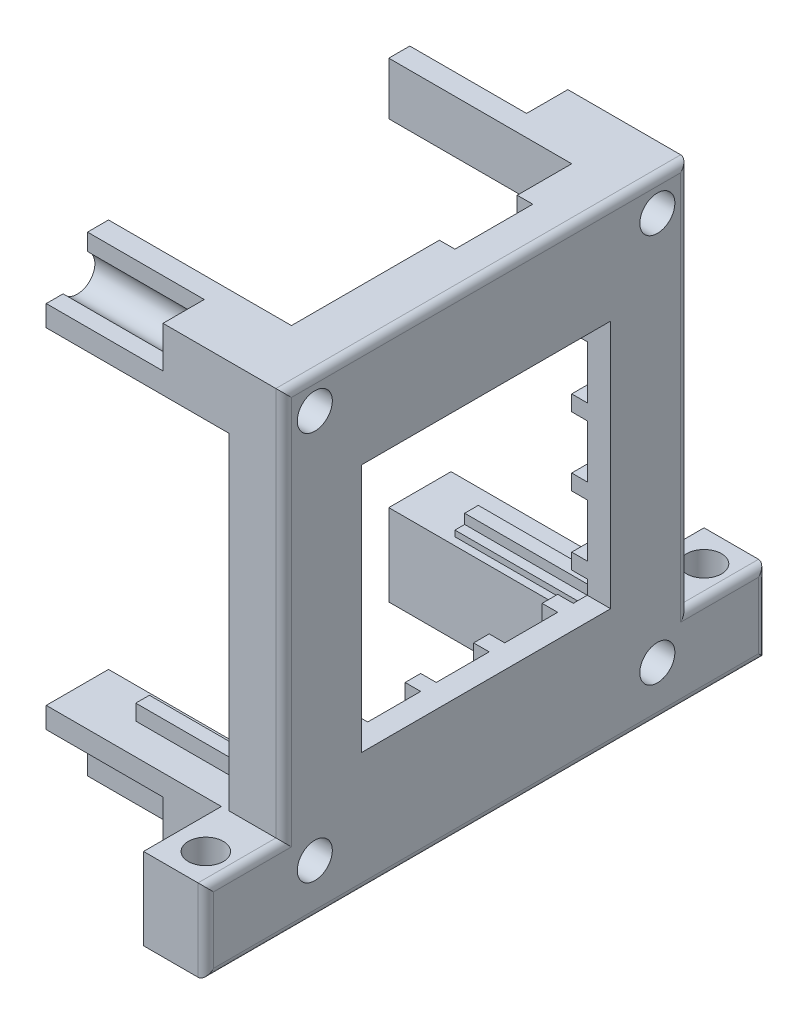
SolidWorks part; units mm, degrees
ref_plane "Front Plane" through (0, 0, 0) normal (0, 0, 1) x (1, 0, 0)
ref_plane "Top Plane" through (0, 0, 0) normal (0, 1, 0) x (1, 0, 0)
ref_plane "Right Plane" through (0, 0, 0) normal (1, 0, 0) x (0, 0, -1)
sketch "Sketch1" plane through (0, 0, 0) normal (1, 0, 0) x (0, 0, -1)
  line L1 (16, -16) -> (-16, -16)
  line L2 (16, -16) -> (16, 16)
  line L3 (16, 16) -> (-16, 16)
  line L4 (-16, -16) -> (-16, 16)
  line L5 (16, -16) -> (-16, 16) construction
  line L6 (16, 16) -> (-16, -16) construction
  line L7 (21, -21) -> (-21, -21) construction
  line L8 (21, -21) -> (21, 21) construction
  line L9 (21, 21) -> (-21, 21) construction
  line L10 (-21, -21) -> (-21, 21) construction
  line L11 (21, -21) -> (-21, 21) construction
  line L12 (21, 21) -> (-21, -21) construction
  line L13 (26, -29) -> (-26, -29)
  line L14 (26, -29) -> (26, 29)
  line L15 (26, 29) -> (-26, 29)
  line L16 (-26, -29) -> (-26, 29)
  line L17 (26, -29) -> (-26, 29) construction
  line L18 (26, 29) -> (-26, -29) construction
  point P0 (0, 0)
  point P6 (0, 0)
  point P11 (0, 0)
  dimension "D1" = 42
  dimension "D2" = 5
  dimension "D3" = 5
  dimension "D4" = 8
extrude "Boss-Extrude1" add sketch "Sketch1" against normal blind 3
sketch "Sketch2" plane through (-3, 0, 0) normal (-1, 0, 0) x (0, 0, 1)
  line L0 (26, 29) -> (26, -29) construction
  line L1 (21, -21) -> (-21, -21)
  line L2 (21, -21) -> (21, 21)
  line L3 (21, 21) -> (-21, 21)
  line L4 (-21, -21) -> (-21, 21)
  line L5 (21, -21) -> (-21, 21) construction
  line L6 (21, 21) -> (-21, -21) construction
  line L7 (26, -29) -> (-26, -29) construction
  line L8 (-26, -29) -> (-26, 29) construction
  line L9 (-26, 29) -> (26, 29) construction
  line L10 (26, 29) -> (26, -29)
  line L11 (26, -29) -> (-26, -29)
  line L12 (-26, -29) -> (-26, 29)
  line L13 (-26, 29) -> (26, 29)
  point P0 (0, 0)
  dimension "D1" = 42
extrude "Boss-Extrude2" add sketch "Sketch2" along normal blind 4
sketch "Sketch3" plane through (-7, 0, 0) normal (-1, 0, 0) x (0, 0, 1)
  line L0 (21, 21) -> (-21, 21) construction
  line L1 (-26, 29) -> (-18, 29)
  line L2 (-26, 29) -> (-26, 21)
  line L3 (-26, 21) -> (-18, 21)
  line L4 (-18, 29) -> (-18, 21)
  dimension "D1" = 8
extrude "Boss-Extrude3" add sketch "Sketch3" along normal blind 23.5
sketch "Sketch4" plane through (0, 0, 0) normal (1, 0, 0) x (0, 0, -1)
  line L0 (26, 29) -> (-26, 29) construction
  line L1 (26, -29) -> (26, 29) construction
  circle A0 centre (22, 25) radius 2.25
  dimension "D1" = 4.5
  dimension "D2" = 4
  dimension "D3" = 4
extrude "Cut-Extrude1" cut sketch "Sketch4" against normal through all
sketch "Sketch5" plane through (-30.5, 0, 0) normal (-1, 0, 0) x (0, 0, 1)
  line L1 (-20.7, 23.7) -> (-26, 23.7)
  line L2 (-20.7, 23.7) -> (-20.7, 29)
  line L3 (-20.7, 29) -> (-26, 29)
  line L4 (-26, 23.7) -> (-26, 29)
  dimension "D1" = 5.3
extrude "Cut-Extrude2" cut sketch "Sketch5" against normal blind 15
mirror "Mirror1" about plane through (0, 0, 0) normal (0, 1, 0) of "Cut-Extrude2", "Boss-Extrude3", "Cut-Extrude1"
mirror "Mirror2" about plane through (0, 0, 0) normal (0, 0, 1) of "Mirror1"
sketch "Sketch6" plane through (-3, 0, 0) normal (-1, 0, 0) x (0, 0, 1)
  line L0 (21, 21) -> (-21, 21) construction
  line L1 (-14.2, 21) -> (-12.2, 21)
  line L2 (-14.2, 21) -> (-14.2, 20.25)
  line L3 (-14.2, 20.25) -> (-12.2, 20.25)
  line L4 (-12.2, 21) -> (-12.2, 20.25)
  line L5 (18, 21) -> (-18, 21) construction
  line L6 (-5.4, 21) -> (-3.4, 21)
  line L7 (-5.4, 21) -> (-5.4, 20.25)
  line L8 (-5.4, 20.25) -> (-3.4, 20.25)
  line L9 (-3.4, 21) -> (-3.4, 20.25)
  line L10 (21, -21) -> (21, 21) construction
  line L11 (3.4, 21) -> (5.4, 21)
  line L12 (3.4, 21) -> (3.4, 20.25)
  line L13 (3.4, 20.25) -> (5.4, 20.25)
  line L14 (5.4, 21) -> (5.4, 20.25)
  line L15 (12.2, 21) -> (14.2, 21)
  line L16 (12.2, 21) -> (12.2, 20.25)
  line L17 (12.2, 20.25) -> (14.2, 20.25)
  line L18 (14.2, 21) -> (14.2, 20.25)
  line L19 (21, 14.2) -> (20.25, 14.2)
  line L20 (21, 14.2) -> (21, 12.2)
  line L21 (21, 12.2) -> (20.25, 12.2)
  line L22 (20.25, 14.2) -> (20.25, 12.2)
  line L23 (21, -21) -> (21, 21) construction
  line L24 (21, 5.4) -> (20.25, 5.4)
  line L25 (21, 5.4) -> (21, 3.4)
  line L26 (21, 3.4) -> (20.25, 3.4)
  line L27 (20.25, 5.4) -> (20.25, 3.4)
  line L28 (-21, 21) -> (-21, -21) construction
  line L29 (-21, 14.2) -> (-20.25, 14.2)
  line L30 (-21, 14.2) -> (-21, 12.2)
  line L31 (-21, 12.2) -> (-20.25, 12.2)
  line L32 (-20.25, 14.2) -> (-20.25, 12.2)
  line L33 (-21, 21) -> (-21, -21) construction
  line L34 (-21, 5.4) -> (-20.25, 5.4)
  line L35 (-21, 5.4) -> (-21, 3.4)
  line L36 (-21, 3.4) -> (-20.25, 3.4)
  line L37 (-20.25, 5.4) -> (-20.25, 3.4)
  line L38 (0, 0) -> (0, 21) construction
  line L39 (-21, 21) -> (-14.2, 21) construction
  line L40 (-12.2, 21) -> (-5.4, 21) construction
  line L41 (-3.4, 21) -> (3.4, 21) construction
  line L42 (5.4, 21) -> (12.2, 21) construction
  line L43 (14.2, 21) -> (21, 21) construction
  line L44 (21, 21) -> (21, 14.2) construction
  line L45 (21, 12.2) -> (21, 5.4) construction
  point P51 (0, 21)
  dimension "D1" = 0.75
  dimension "D2" = 2
extrude "Boss-Extrude4" add sketch "Sketch6" along normal up to surface (4 mm away) up to face at (-7, 0, -23.5)
sketch "Sketch7" plane through (-3, 0, 0) normal (-1, 0, 0) x (0, 0, 1)
  line L0 (-16, -16) -> (-16, 16) construction
  line L1 (-20.25, 3.4) -> (-16, 3.4)
  line L2 (-20.25, 3.4) -> (-20.25, 5.4)
  line L3 (-20.25, 5.4) -> (-16, 5.4)
  line L4 (-16, 3.4) -> (-16, 5.4)
  line L5 (-16, 16) -> (16, 16) construction
  line L6 (-20.25, 12.2) -> (-16, 12.2)
  line L7 (-20.25, 12.2) -> (-20.25, 14.2)
  line L8 (-20.25, 14.2) -> (-16, 14.2)
  line L9 (-16, 12.2) -> (-16, 14.2)
  line L10 (-14.2, 20.25) -> (-12.2, 20.25)
  line L11 (-14.2, 20.25) -> (-14.2, 16)
  line L12 (-14.2, 16) -> (-12.2, 16)
  line L13 (-12.2, 20.25) -> (-12.2, 16)
  line L14 (16, 16) -> (16, -16) construction
  line L15 (-5.4, 20.25) -> (-3.4, 20.25)
  line L16 (-5.4, 20.25) -> (-5.4, 16)
  line L17 (-5.4, 16) -> (-3.4, 16)
  line L18 (-3.4, 20.25) -> (-3.4, 16)
  line L19 (3.4, 20.25) -> (5.4, 20.25)
  line L20 (3.4, 20.25) -> (3.4, 16)
  line L21 (3.4, 16) -> (5.4, 16)
  line L22 (5.4, 20.25) -> (5.4, 16)
  line L23 (12.2, 20.25) -> (14.2, 20.25)
  line L24 (12.2, 20.25) -> (12.2, 16)
  line L25 (12.2, 16) -> (14.2, 16)
  line L26 (14.2, 20.25) -> (14.2, 16)
  line L27 (20.25, 14.2) -> (16, 14.2)
  line L28 (20.25, 14.2) -> (20.25, 12.2)
  line L29 (20.25, 12.2) -> (16, 12.2)
  line L30 (16, 14.2) -> (16, 12.2)
  line L31 (21, 3.4) -> (20.25, 3.4) construction
  line L32 (20.25, 5.4) -> (16, 5.4)
  line L33 (20.25, 5.4) -> (20.25, 3.4)
  line L34 (20.25, 3.4) -> (16, 3.4)
  line L35 (16, 5.4) -> (16, 3.4)
  line L36 (20.25, 12.2) -> (21, 12.2) construction
  line L37 (14.2, 21) -> (14.2, 20.25) construction
  line L38 (5.4, 21) -> (5.4, 20.25) construction
  line L39 (-3.4, 21) -> (-3.4, 20.25) construction
  line L40 (-12.2, 20.25) -> (-12.2, 21) construction
  line L41 (-21, 14.2) -> (-20.25, 14.2) construction
  line L42 (-20.25, 5.4) -> (-21, 5.4) construction
extrude "Boss-Extrude5" add sketch "Sketch7" along normal blind 2
mirror "Mirror3" about plane through (0, 0, 0) normal (0, 1, 0) of "Boss-Extrude5", "Boss-Extrude4"
sketch "Sketch8" plane through (-30.5, 0, 0) normal (-1, 0, 0) x (0, 0, 1)
  line L0 (-21, 21) -> (-21, 14.2) construction
  line L1 (-21, 20.25) -> (21, 20.25)
  line L2 (-21, 20.25) -> (-21, 22.25)
  line L3 (-21, 22.25) -> (21, 22.25)
  line L4 (21, 20.25) -> (21, 22.25)
  line L5 (-3.4, 20.25) -> (-5.4, 20.25) construction
  line L6 (21, 14.2) -> (21, 21) construction
  dimension "D1" = 2
extrude "Cut-Extrude3" cut sketch "Sketch8" against normal up to surface (25.5 mm away) up to face at (-5, 18.125, -13.2)
sketch "Sketch9" plane through (-3, 0, 0) normal (-1, 0, 0) x (0, 0, 1)
  line L0 (-22, -21) -> (-22, -19)
  line L2 (-22, -19) -> (-20.25, -19)
  line L3 (-20.25, -19) -> (-20.25, -20.25)
  line L4 (-20.25, -20.25) -> (-19, -20.25)
  line L5 (-19, -20.25) -> (-19, -21)
  line L6 (-18, -21) -> (-14.2, -21) construction
  line L7 (-19, -21) -> (-22, -21)
  line L8 (-20.25, -14.2) -> (-20.25, -12.2) construction
  line L9 (-12.2, -20.25) -> (-14.2, -20.25) construction
  line L10 (-21, -14.2) -> (-21, -21) construction
  dimension "D1" = 2
  dimension "D2" = 3
  dimension "D3" = 1
extrude "Boss-Extrude6" add sketch "Sketch9" along normal blind 20
mirror "Mirror4" about plane through (0, 0, 0) normal (0, 0, 1) of "Boss-Extrude6"
sketch "Sketch10" plane through (0, -29, 0) normal (0, -1, 0) x (1, 0, 0)
  line L0 (0, 28) -> (-8, 36) construction
  line L1 (0, 26) -> (-8, 26)
  line L2 (0, 26) -> (0, 36)
  line L3 (0, 36) -> (-8, 36)
  line L4 (-8, 26) -> (-8, 36)
  circle A0 centre (-4, 32) radius 2.25
  dimension "D1" = 4.5
  dimension "D2" = 10
  dimension "D3" = 8
  dimension "D4" = 8
extrude "Boss-Extrude7" add sketch "Sketch10" against normal up to surface (8 mm away) up to face at (-14.1, -21, 19.84)
mirror "Mirror5" about plane through (0, 0, 0) normal (0, 0, 1) of "Boss-Extrude7"
sketch "Sketch11" plane through (-7, 0, 0) normal (-1, 0, 0) x (0, 0, 1)
  line L0 (-18, 22.25) -> (18, 22.25) construction
  line L1 (-11, 22.25) -> (-1, 22.25)
  line L2 (-11, 22.25) -> (-11, 30.25)
  line L3 (-11, 30.25) -> (-1, 30.25)
  line L4 (-1, 22.25) -> (-1, 30.25)
  line L5 (-18, 22.25) -> (-18, 29) construction
  dimension "D1" = 10
  dimension "D2" = 8
  dimension "D3" = 7
extrude "Cut-Extrude4" cut sketch "Sketch11" against normal blind 2
sketch "Sketch12" plane through (0, -29, 0) normal (0, -1, 0) x (1, 0, 0)
  line L16 (-15.5, 20.7) -> (-30.5, 20.7)
  line L17 (-30.5, 20.7) -> (-30.5, 18)
  line L18 (-30.5, 18) -> (-7, 18)
  line L19 (-7, 18) -> (-7, -18)
  line L20 (-7, -18) -> (-30.5, -18)
  line L21 (-30.5, -18) -> (-30.5, -20.7)
  line L22 (-30.5, -20.7) -> (-15.5, -20.7)
  line L23 (-15.5, -20.7) -> (-15.5, -26)
  line L24 (-15.5, -26) -> (-8, -26)
  line L25 (-8, -26) -> (-8, -36)
  line L26 (-8, -36) -> (0, -36)
  line L27 (0, -36) -> (0, 36)
  line L28 (0, 36) -> (-8, 36)
  line L29 (-8, 36) -> (-8, 26)
  line L30 (-8, 26) -> (-15.5, 26)
  line L31 (-15.5, 26) -> (-15.5, 20.7)
  line L32 (-15.5, 20.7) -> (-30.5, 20.7)
  line L33 (-30.5, 20.7) -> (-30.5, 18)
  line L34 (-30.5, 18) -> (-7, 18)
  line L35 (-7, 18) -> (-7, -18)
  line L36 (-7, -18) -> (-30.5, -18)
  line L37 (-30.5, -18) -> (-30.5, -20.7)
  line L38 (-30.5, -20.7) -> (-15.5, -20.7)
  line L39 (-15.5, -20.7) -> (-15.5, -26)
  line L40 (-15.5, -26) -> (-8, -26)
  line L41 (-8, -26) -> (-8, -36)
  line L42 (-8, -36) -> (0, -36)
  line L43 (0, -36) -> (0, 36)
  line L44 (0, 36) -> (-8, 36)
  line L45 (-8, 36) -> (-8, 26)
  line L46 (-8, 26) -> (-15.5, 26)
  line L47 (-15.5, 26) -> (-15.5, 20.7)
  dimension "D1" = 0
extrude "Boss-Extrude8" add sketch "Sketch12" along normal blind 2.5
fillet "Fillet1" radius 1 8 edges at (0, 4, -26) (0, -21, -31) (0, -26.25, -36) (0, -21, 31) (0, -31.5, 0) (0, -26.25, 36) (0, 4, 26) (0, 29, 0)
